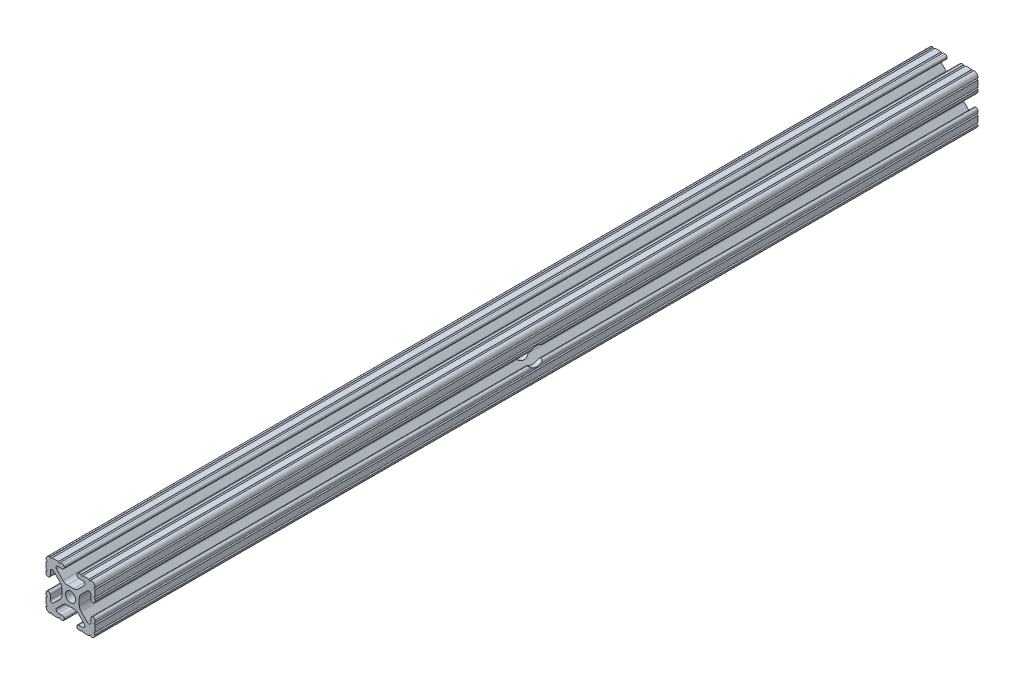
SolidWorks part; units mm, degrees
ref_plane "Front Plane" through (0, 0, 0) normal (0, 0, 1) x (1, 0, 0)
ref_plane "Top Plane" through (0, 0, 0) normal (0, 1, 0) x (1, 0, 0)
ref_plane "Right Plane" through (0, 0, 0) normal (1, 0, 0) x (0, 0, -1)
sketch "Sketch1" plane through (0, 0, 0) normal (0, 0, 1) x (1, 0, 0)
  line L88 (-7.1797, -8.6452) -> (-3.9523, -5.4237)
  line L89 (-1.7093, -4.4958) -> (1.7093, -4.4958)
  line L90 (3.9523, -5.4237) -> (7.1797, -8.6452)
  line L91 (6.4164, -10.4902) -> (4.2875, -10.4902)
  line L92 (3.2385, -11.5392) -> (3.2385, -11.651)
  line L93 (4.2875, -12.7) -> (5.3171, -12.7)
  line L94 (6.3331, -12.7) -> (9.5504, -12.7)
  line L95 (12.7, -9.5504) -> (12.7, -6.3331)
  line L96 (12.7, -5.3171) -> (12.7, -4.2875)
  line L97 (11.651, -3.2385) -> (11.5392, -3.2385)
  line L98 (10.4902, -4.2875) -> (10.4902, -6.4021)
  line L99 (8.7371, -7.1294) -> (5.441, -3.8408)
  line L100 (4.5085, -1.5932) -> (4.5085, 1.5932)
  line L101 (5.441, 3.8408) -> (8.7371, 7.1294)
  line L102 (10.4902, 6.4021) -> (10.4902, 4.2875)
  line L103 (11.5392, 3.2385) -> (11.651, 3.2385)
  line L104 (12.7, 4.2875) -> (12.7, 5.3171)
  line L105 (12.7, 6.3331) -> (12.7, 9.5504)
  line L106 (9.5504, 12.7) -> (6.3331, 12.7)
  line L107 (5.3171, 12.7) -> (4.2875, 12.7)
  line L108 (3.2385, 11.651) -> (3.2385, 11.5392)
  line L109 (4.2875, 10.4902) -> (6.4768, 10.4902)
  line L110 (7.207, 8.7244) -> (3.8983, 5.4232)
  line L111 (1.6558, 4.4958) -> (-1.6558, 4.4958)
  line L112 (-3.8983, 5.4232) -> (-7.207, 8.7244)
  line L113 (-6.4768, 10.4902) -> (-4.2875, 10.4902)
  line L114 (-3.2385, 11.5392) -> (-3.2385, 11.651)
  line L115 (-4.2875, 12.7) -> (-5.3171, 12.7)
  line L116 (-6.3331, 12.7) -> (-9.5504, 12.7)
  line L117 (-12.7, 9.5504) -> (-12.7, 6.3331)
  line L118 (-12.7, 5.3171) -> (-12.7, 4.2875)
  line L119 (-11.651, 3.2385) -> (-11.5392, 3.2385)
  line L120 (-10.4902, 4.2875) -> (-10.4902, 6.4021)
  line L121 (-8.7371, 7.1294) -> (-5.441, 3.8408)
  line L122 (-4.5085, 1.5932) -> (-4.5085, -1.5932)
  line L123 (-5.441, -3.8408) -> (-8.7371, -7.1294)
  line L124 (-10.4902, -6.4021) -> (-10.4902, -4.2875)
  line L125 (-11.5392, -3.2385) -> (-11.651, -3.2385)
  line L126 (-12.7, -4.2875) -> (-12.7, -5.3171)
  line L127 (-12.7, -6.3331) -> (-12.7, -9.5504)
  line L128 (-9.5504, -12.7) -> (-6.3331, -12.7)
  line L129 (-5.3171, -12.7) -> (-4.2875, -12.7)
  line L130 (-3.2385, -11.651) -> (-3.2385, -11.5392)
  line L131 (-4.2875, -10.4902) -> (-6.4164, -10.4902)
  circle A1 centre (0, 0) radius 2.6035
  arc A104 (-7.1797, -8.6452) -> (-6.4164, -10.4902) centre (-6.4164, -9.4098) ccw
  arc A105 (-1.7093, -4.4958) -> (-3.9523, -5.4237) centre (-1.7093, -7.6708) ccw
  arc A106 (3.9523, -5.4237) -> (1.7093, -4.4958) centre (1.7093, -7.6708) ccw
  arc A107 (6.4164, -10.4902) -> (7.1797, -8.6452) centre (6.4164, -9.4098) ccw
  arc A108 (4.2875, -10.4902) -> (3.2385, -11.5392) centre (4.2875, -11.5392) ccw
  arc A109 (3.2385, -11.651) -> (4.2875, -12.7) centre (4.2875, -11.651) ccw
  arc A110 (6.3331, -12.7) -> (5.3171, -12.7) centre (5.8251, -12.7) ccw
  arc A111 (10.5664, -12.6998) -> (9.5504, -12.7) centre (10.0584, -12.7) ccw
  arc A112 (10.5664, -12.6998) -> (12.6998, -10.5664) centre (10.5918, -10.5918) ccw
  arc A113 (12.7, -9.5504) -> (12.6998, -10.5664) centre (12.7, -10.0584) ccw
  arc A114 (12.7, -5.3171) -> (12.7, -6.3331) centre (12.7, -5.8251) ccw
  arc A115 (12.7, -4.2875) -> (11.651, -3.2385) centre (11.651, -4.2875) ccw
  arc A116 (11.5392, -3.2385) -> (10.4902, -4.2875) centre (11.5392, -4.2875) ccw
  arc A117 (8.7371, -7.1294) -> (10.4902, -6.4021) centre (9.4628, -6.4021) ccw
  arc A118 (4.5085, -1.5932) -> (5.441, -3.8408) centre (7.6835, -1.5932) ccw
  arc A119 (5.441, 3.8408) -> (4.5085, 1.5932) centre (7.6835, 1.5932) ccw
  arc A120 (10.4902, 6.4021) -> (8.7371, 7.1294) centre (9.4628, 6.4021) ccw
  arc A121 (10.4902, 4.2875) -> (11.5392, 3.2385) centre (11.5392, 4.2875) ccw
  arc A122 (11.651, 3.2385) -> (12.7, 4.2875) centre (11.651, 4.2875) ccw
  arc A123 (12.7, 6.3331) -> (12.7, 5.3171) centre (12.7, 5.8251) ccw
  arc A124 (12.6998, 10.5664) -> (12.7, 9.5504) centre (12.7, 10.0584) ccw
  arc A125 (12.6998, 10.5664) -> (10.5664, 12.6998) centre (10.5918, 10.5918) ccw
  arc A126 (9.5504, 12.7) -> (10.5664, 12.6998) centre (10.0584, 12.7) ccw
  arc A127 (5.3171, 12.7) -> (6.3331, 12.7) centre (5.8251, 12.7) ccw
  arc A128 (4.2875, 12.7) -> (3.2385, 11.651) centre (4.2875, 11.651) ccw
  arc A129 (3.2385, 11.5392) -> (4.2875, 10.4902) centre (4.2875, 11.5392) ccw
  arc A130 (7.207, 8.7244) -> (6.4768, 10.4902) centre (6.4768, 9.4563) ccw
  arc A131 (1.6558, 4.4958) -> (3.8983, 5.4232) centre (1.6558, 7.6708) ccw
  arc A132 (-3.8983, 5.4232) -> (-1.6558, 4.4958) centre (-1.6558, 7.6708) ccw
  arc A133 (-6.4768, 10.4902) -> (-7.207, 8.7244) centre (-6.4768, 9.4563) ccw
  arc A134 (-4.2875, 10.4902) -> (-3.2385, 11.5392) centre (-4.2875, 11.5392) ccw
  arc A135 (-3.2385, 11.651) -> (-4.2875, 12.7) centre (-4.2875, 11.651) ccw
  arc A136 (-6.3331, 12.7) -> (-5.3171, 12.7) centre (-5.8251, 12.7) ccw
  arc A137 (-10.5664, 12.6998) -> (-9.5504, 12.7) centre (-10.0584, 12.7) ccw
  arc A138 (-10.5664, 12.6998) -> (-12.6998, 10.5664) centre (-10.5918, 10.5918) ccw
  arc A139 (-12.7, 9.5504) -> (-12.6998, 10.5664) centre (-12.7, 10.0584) ccw
  arc A140 (-12.7, 5.3171) -> (-12.7, 6.3331) centre (-12.7, 5.8251) ccw
  arc A141 (-12.7, 4.2875) -> (-11.651, 3.2385) centre (-11.651, 4.2875) ccw
  arc A142 (-11.5392, 3.2385) -> (-10.4902, 4.2875) centre (-11.5392, 4.2875) ccw
  arc A143 (-8.7371, 7.1294) -> (-10.4902, 6.4021) centre (-9.4628, 6.4021) ccw
  arc A144 (-4.5085, 1.5932) -> (-5.441, 3.8408) centre (-7.6835, 1.5932) ccw
  arc A145 (-5.441, -3.8408) -> (-4.5085, -1.5932) centre (-7.6835, -1.5932) ccw
  arc A146 (-10.4902, -6.4021) -> (-8.7371, -7.1294) centre (-9.4628, -6.4021) ccw
  arc A147 (-10.4902, -4.2875) -> (-11.5392, -3.2385) centre (-11.5392, -4.2875) ccw
  arc A148 (-11.651, -3.2385) -> (-12.7, -4.2875) centre (-11.651, -4.2875) ccw
  arc A149 (-12.7, -6.3331) -> (-12.7, -5.3171) centre (-12.7, -5.8251) ccw
  arc A150 (-12.6998, -10.5664) -> (-12.7, -9.5504) centre (-12.7, -10.0584) ccw
  arc A151 (-12.6998, -10.5664) -> (-10.5664, -12.6998) centre (-10.5918, -10.5918) ccw
  arc A152 (-9.5504, -12.7) -> (-10.5664, -12.6998) centre (-10.0584, -12.7) ccw
  arc A153 (-5.3171, -12.7) -> (-6.3331, -12.7) centre (-5.8251, -12.7) ccw
  arc A154 (-4.2875, -12.7) -> (-3.2385, -11.651) centre (-4.2875, -11.651) ccw
  arc A155 (-3.2385, -11.5392) -> (-4.2875, -10.4902) centre (-4.2875, -11.5392) ccw
extrude "Boss-Extrude1" add sketch "Sketch1" along normal mid plane 457.2
sketch "Sketch2" plane through (12.7, 0, 0) normal (1, 0, 0) x (0, 0, -1)
  circle A0 centre (0, 0) radius 4.7625
  dimension "D1" = 9.525
extrude "Cut-Extrude1" cut sketch "Sketch2" against normal through all
